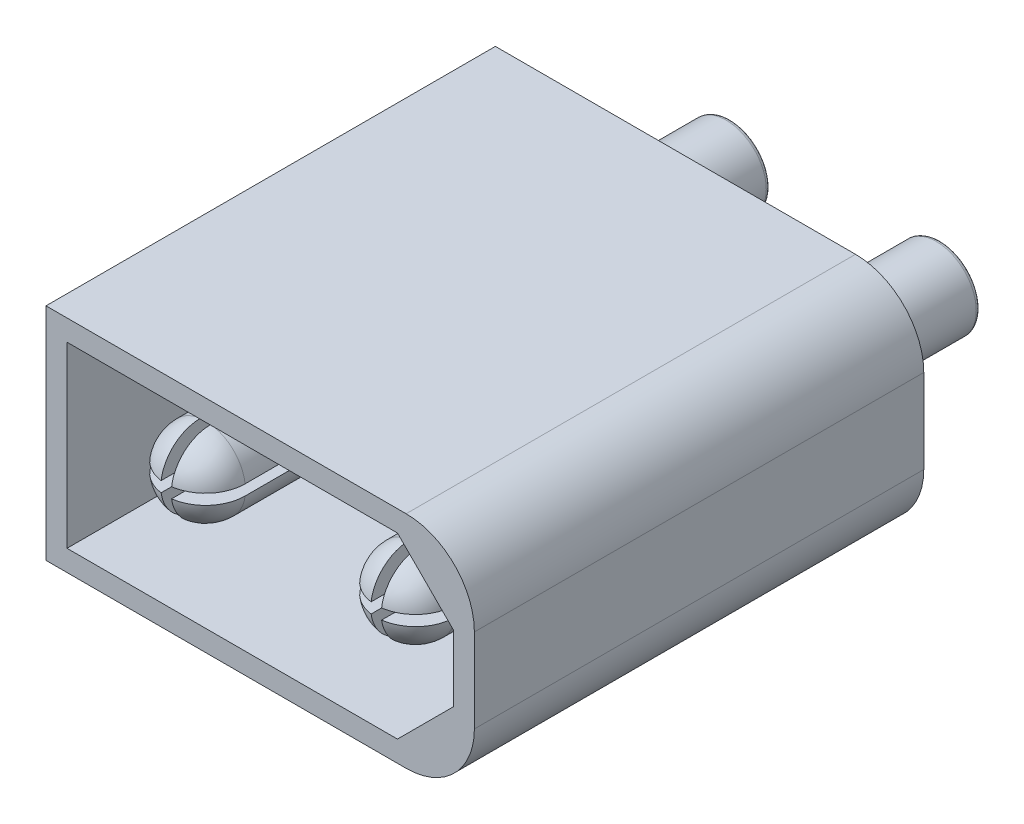
SolidWorks part; units mm, degrees
ref_plane "Front Plane" through (0, 0, 0) normal (0, 0, 1) x (1, 0, 0)
ref_plane "Top Plane" through (0, 0, 0) normal (0, 1, 0) x (1, 0, 0)
ref_plane "Right Plane" through (0, 0, 0) normal (1, 0, 0) x (0, 0, -1)
sketch "Sketch1" plane through (0, 0, 0) normal (0, 0, 1) x (1, 0, 0)
  line L0 (0, 0) -> (10.2, 0) construction
  line L1 (0, -2.625) -> (0, 2.625)
  line L2 (0, 2.625) -> (8.575, 2.625)
  line L4 (10.2, 1) -> (10.2, -1)
  line L5 (5.1, 0) -> (5.1, 1.3562) construction
  line L7 (0, -2.625) -> (8.575, -2.625)
  line L8 (0.5, 2.125) -> (8.3679, 2.125)
  line L9 (8.3679, 2.125) -> (9.7, 0.7929)
  line L10 (9.7, 0.7929) -> (9.7, -0.7929)
  line L11 (8.3679, -2.125) -> (9.7, -0.7929)
  line L12 (0.5, -2.125) -> (8.3679, -2.125)
  line L13 (0.5, -2.125) -> (0.5, 2.125)
  line L14 (8.575, 2.625) -> (10.2, 1) construction
  line L15 (8.575, -2.625) -> (10.2, -1) construction
  circle A0 centre (2.6, 0) radius 0.95
  circle A2 centre (7.6, 0) radius 0.95
  arc A3 (8.575, 2.625) -> (10.2, 1) centre (8.575, 1) cw
  arc A4 (8.575, -2.625) -> (10.2, -1) centre (8.575, -1) ccw
  dimension "D6" = 1.9
  dimension "D1" = 5.25
  dimension "D2" = 10.2
  dimension "D3" = 135
  dimension "D4" = 2.5
  dimension "D7" = 2
  dimension "D5" = 0.5
extrude "Boss-Extrude1" add sketch "Sketch1" along normal blind 10.7 contours L1 L7 A4 L4 A3 L2 L12 L13 L8 L9 L10 L11 region at (0.1147, 0, 0)
extrude "Boss-Extrude5" add sketch "Sketch1<4>" along normal blind 9.5 and the other way blind 3 separate body contours A0 | A2 region at (2.6, 0, 0)
sketch "Sketch1<4>" plane through (0, 0, 0) normal (0, 0, 1) x (1, 0, 0) same geometry as "Sketch1"
ref_plane "Plane1" through (0, 0, 1) normal (0, 0, -1) x (-1, 0, 0)
sketch "Sketch3" plane through (0, 0, 1) normal (0, 0, -1) x (-1, 0, 0)
  line L0 (-0.5, -2.125) -> (-0.5, 2.125) construction
  line L1 (-0.5, -2.125) -> (-8.3679, -2.125) construction
  line L2 (-8.3679, -2.125) -> (-9.7, -0.7929) construction
  line L3 (-9.7, 0.7929) -> (-9.7, -0.7929) construction
  line L4 (-8.3679, 2.125) -> (-9.7, 0.7929) construction
  line L5 (-0.5, 2.125) -> (-8.3679, 2.125) construction
  line L6 (-0.5, -2.125) -> (-0.5, 2.125)
  line L7 (-0.5, -2.125) -> (-8.3679, -2.125)
  line L8 (-8.3679, -2.125) -> (-9.7, -0.7929)
  line L9 (-9.7, 0.7929) -> (-9.7, -0.7929)
  line L10 (-8.3679, 2.125) -> (-9.7, 0.7929)
  line L11 (-0.5, 2.125) -> (-8.3679, 2.125)
extrude "Boss-Extrude3" add sketch "Sketch3" against normal blind 2.5
dome "Dome1" faces to dome 1 distance 0.95 reverse direction no elliptical dome no face at (6.65, 0, 9.5) parameters "D1"=0.95
dome "Dome2" faces to dome 1 distance 0.95 reverse direction no elliptical dome no face at (3.55, 0, 9.5) parameters "D1"=0.95
ref_plane "Plane2" through (0, 0, 6) normal (0, 0, 1) x (1, 0, 0)
sketch "Sketch4" plane through (0, 0, 6) normal (0, 0, 1) x (1, 0, 0)
  line L0 (7.6, 0) -> (2.6, 0) construction
  line L1 (5.1, 0) -> (5.1, -4.8964) construction
  line L2 (7.6, 0) -> (7.6, 0.95) construction
  line L3 (7.475, 0.9417) -> (7.475, 0.125)
  line L4 (7.725, 0.9417) -> (7.725, 0.125)
  line L5 (8.5417, -0.125) -> (7.725, -0.125)
  line L6 (8.5417, 0.125) -> (7.725, 0.125)
  line L7 (7.475, -0.9417) -> (7.475, -0.125)
  line L8 (7.725, -0.9417) -> (7.725, -0.125)
  line L9 (6.6583, 0.125) -> (7.475, 0.125)
  line L10 (6.6583, -0.125) -> (7.475, -0.125)
  line L11 (2.6, 0) -> (2.6, 0.95) construction
  line L12 (3.5417, -0.125) -> (2.725, -0.125)
  line L13 (3.5417, 0.125) -> (2.725, 0.125)
  line L14 (2.475, -0.9417) -> (2.475, -0.125)
  line L15 (2.725, -0.9417) -> (2.725, -0.125)
  line L16 (1.6583, 0.125) -> (2.475, 0.125)
  line L17 (1.6583, -0.125) -> (2.475, -0.125)
  line L18 (2.475, 0.9417) -> (2.475, 0.125)
  line L19 (2.725, 0.9417) -> (2.725, 0.125)
  circle A0 centre (7.6, 0) radius 0.95 construction
  circle A1 centre (2.6, 0) radius 0.95 construction
  arc A2 (7.725, 0.9417) -> (7.475, 0.9417) centre (7.6, 0) ccw
  circle A3 centre (2.6, 0) radius 0.95 construction
  arc A4 (8.5417, -0.125) -> (8.5417, 0.125) centre (7.6, 0) ccw
  arc A5 (7.475, -0.9417) -> (7.725, -0.9417) centre (7.6, 0) ccw
  arc A6 (6.6583, 0.125) -> (6.6583, -0.125) centre (7.6, 0) ccw
  arc A7 (3.5417, 0.125) -> (3.5417, -0.125) centre (2.6, 0) cw
  arc A8 (2.725, -0.9417) -> (2.475, -0.9417) centre (2.6, 0) cw
  arc A9 (1.6583, -0.125) -> (1.6583, 0.125) centre (2.6, 0) cw
  arc A10 (2.475, 0.9417) -> (2.725, 0.9417) centre (2.6, 0) cw
  point P28 (7.6, 0)
  dimension "D1" = 0.25
  dimension "D2" = 4
extrude "Cut-Extrude1" cut sketch "Sketch4" along normal through all
fillet "Fillet2" radius 0.1 1 edges at (6.65, 0, -3)
fillet "Fillet3" radius 0.1 1 edges at (3.55, 0, -3)
